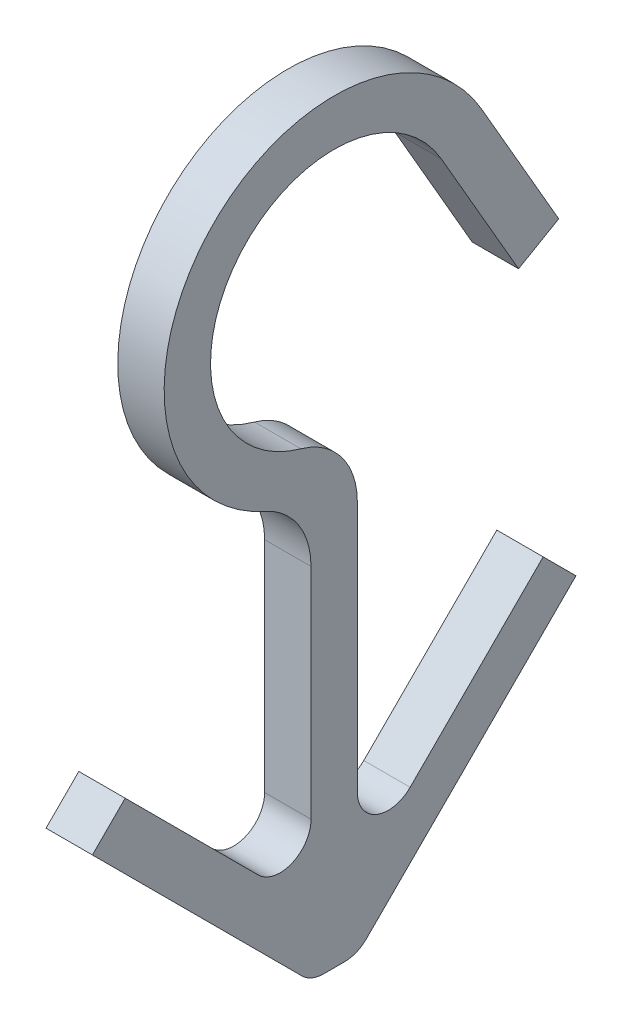
SolidWorks part; units mm, degrees
ref_plane "Front Plane" through (0, 0, 0) normal (0, 0, 1) x (1, 0, 0)
ref_plane "Top Plane" through (0, 0, 0) normal (0, 1, 0) x (1, 0, 0)
ref_plane "Right Plane" through (0, 0, 0) normal (1, 0, 0) x (0, 0, -1)
sketch "Sketch1" plane through (0, 0, 0) normal (1, 0, 0) x (0, 0, -1)
  circle A2 centre (0, 0) radius 22
  circle A3 centre (0, 0) radius 16
  dimension "D1" = 44
  dimension "D2" = 6
extrude "Boss-Extrude1" add sketch "Sketch1" along normal blind 6
sketch "Sketch2" plane through (6, 0, 0) normal (1, 0, 0) x (0, 0, -1)
  line L0 (19.0526, 11) -> (29.0526, -6.3205)
  line L1 (29.0526, -6.3205) -> (23.8564, -9.3205)
  line L2 (23.8564, -9.3205) -> (13.8564, 8)
  line L3 (13.8564, 8) -> (19.0526, 11)
  line L4 (0, 0) -> (0, 16) construction
  circle A0 centre (0, 0) radius 22 construction
  circle A1 centre (0, 0) radius 16 construction
  dimension "D1" = 20
  dimension "D2" = 30
extrude "Boss-Extrude2" add sketch "Sketch2" against normal up to surface (6 mm away) up to face at (0, 0, -22)
sketch "Sketch3" plane through (6, 0, 0) normal (1, 0, 0) x (0, 0, -1)
  line L0 (4.1411, -15.4548) -> (5.694, -21.2504)
  line L1 (0, 0) -> (0, -22) construction
  line L2 (21.4062, -5.0767) -> (13.8564, 8)
  line L3 (21.4062, -5.0767) -> (23.8564, -9.3205) construction
  circle A0 centre (0, 0) radius 16
  circle A1 centre (0, 0) radius 22
  circle A2 centre (0, 0) radius 16 construction
  arc A3 (19.0526, 11) -> (21.4062, -5.0767) centre (0, 0) ccw construction
  circle M6 centre (0, 0) radius 16
  arc M8 (19.0526, 11) -> (21.4062, -5.0767) centre (0, 0) ccw
  dimension "D1" = 15
extrude "Cut-Extrude1" cut sketch "Sketch3" against normal through all contours L2 L0 M8 M6 region at (6, -10.8295, -13.8271)
sketch "Sketch4" plane through (6, 0, 0) normal (1, 0, 0) x (0, 0, -1)
  line L1 (-3, -15.7162) -> (3, -15.7162)
  line L2 (-3, -15.7162) -> (-3, -45.7162)
  line L3 (-3, -45.7162) -> (3, -45.7162)
  line L4 (3, -15.7162) -> (3, -45.7162)
  arc A0 (13.8564, 8) -> (4.1411, -15.4548) centre (0, 0) ccw construction
  point P7 (0, -15.7162)
  dimension "D1" = 6
  dimension "D2" = 30
extrude "Boss-Extrude3" add sketch "Sketch4" against normal up to surface (6 mm away) up to face at (0, -1.6586, -6.5289)
sketch "Sketch5" plane through (6, 0, 0) normal (1, 0, 0) x (0, 0, -1)
  line L0 (3, -21.7945) -> (3, -15.7162)
  line L1 (3, -15.7162) -> (4.1411, -15.4548)
  line L2 (4.1411, -15.4548) -> (5.694, -21.2504)
  arc A0 (3, -21.7945) -> (5.694, -21.2504) centre (3, -14.8533) ccw
extrude "Cut-Extrude2" cut sketch "Sketch5" against normal through all
fillet "Fillet1" radius 10 2 edges at (3, -15.7162, -3) (3, -21.7945, 3)
fillet "Fillet2" radius 10 1 edges at (3, -15.7162, 3)
sketch "Sketch6" plane through (0, 0, 0) normal (-1, 0, 0) x (0, 0, 1)
  line L0 (3, -45.7162) -> (3, -29.2404) construction
  line L1 (-3, -45.7162) -> (3, -45.7162)
  line L2 (-3, -45.7162) -> (-3, -75.7162)
  line L3 (-3, -75.7162) -> (3, -75.7162)
  line L4 (3, -45.7162) -> (3, -75.7162)
  line L5 (3, -67.231) -> (27.0416, -43.1893)
  line L6 (27.0416, -43.1893) -> (31.2843, -47.432)
  line L7 (31.2843, -47.432) -> (3, -75.7162)
  line L8 (3, -67.231) -> (3, -75.7162)
  line M12 (-3, -45.7162) -> (3, -45.7162)
  dimension "D1" = 30
  dimension "D2" = 6
  dimension "D3" = 45
  dimension "D4" = 40
extrude "Boss-Extrude4" add sketch "Sketch6" against normal up to surface (6 mm away) contours L7 L6 L5 L4 | L4 L2 L3 M12 region at (0, -60.7162, 0) region at (0, -58.4781, 16.1101) up to face at (6, -14.2976, -3.6721)
mirror "Mirror1" about plane through (0, 0, 0) normal (0, 0, 1) of "Boss-Extrude4"
fillet "Fillet3" radius 4 4 edges at (3, -67.231, 3) (3, -67.231, -3) (3, -75.7162, 3) (3, -75.7162, -3)
